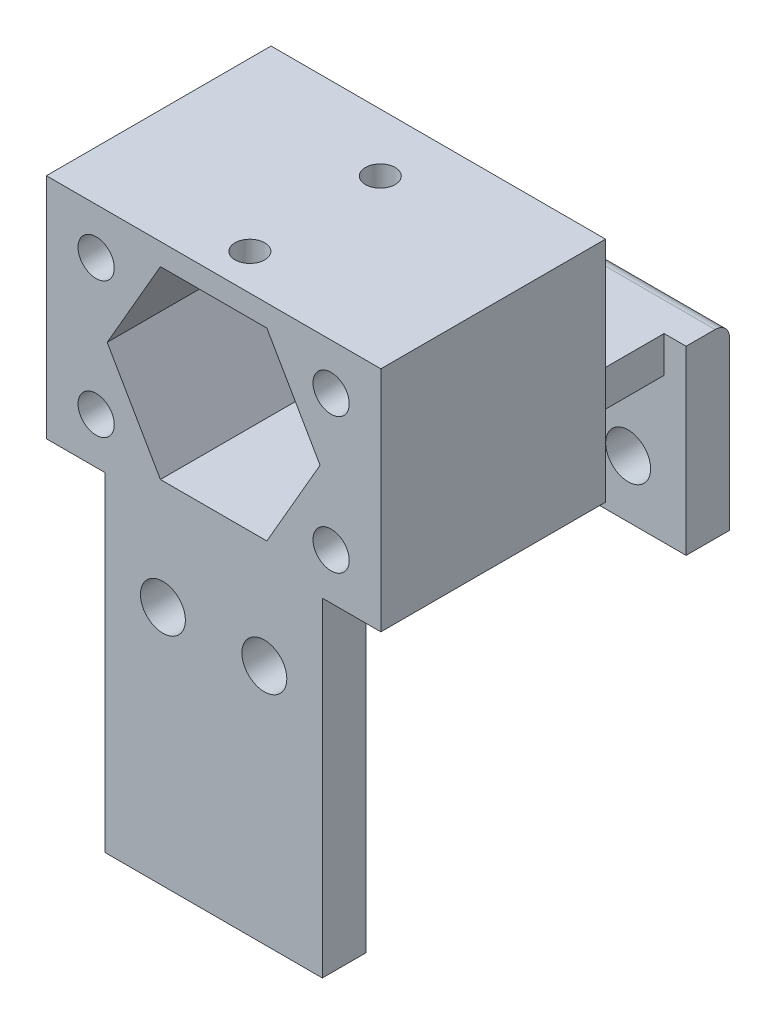
SolidWorks part; units mm, degrees
note: The reader was unsure of these and kept them because the rebuilt part matched: shared geometry of "Sketch8<2>".
other "Markup1"
sketch "Sketch23" plane through (-10.538, -17.86, 12) normal (0, 0, 1) x (1, 0, 0)
material "6061-T6 (SS)"
ref_plane "Front Plane" through (0, 0, 0) normal (0, 0, 1) x (1, 0, 0)
ref_plane "Top Plane" through (0, 0, 0) normal (0, 1, 0) x (1, 0, 0)
ref_plane "Right Plane" through (0, 0, 0) normal (1, 0, 0) x (0, 0, -1)
sketch "Sketch1" plane through (0, 0, 0) normal (0, 0, 1) x (1, 0, 0)
  line L1 (7.3439, 0) -> (3.6719, 6.36)
  line L2 (3.6719, 6.36) -> (-3.6719, 6.36)
  line L3 (-3.6719, 6.36) -> (-7.3439, 0)
  line L4 (-7.3439, 0) -> (-3.6719, -6.36)
  line L5 (-3.6719, -6.36) -> (3.6719, -6.36)
  line L6 (3.6719, -6.36) -> (7.3439, 0)
  line L7 (9.0759, 0) -> (4.538, 7.86)
  line L8 (4.538, 7.86) -> (-4.538, 7.86)
  line L9 (-4.538, 7.86) -> (-9.0759, 0)
  line L10 (-9.0759, 0) -> (-4.538, -7.86)
  line L11 (-4.538, -7.86) -> (4.538, -7.86)
  line L12 (4.538, -7.86) -> (9.0759, 0)
  circle A0 centre (0, 0) radius 6.36 construction
  circle A1 centre (0, 0) radius 7.86 construction
  dimension "D2" = 12.72
  dimension "D1" = 1.5
extrude "Boss-Extrude1" add sketch "Sketch1" along normal blind 14
sketch "Sketch2" plane through (0, 0, 0) normal (0, 0, -1) x (-1, 0, 0)
  line L0 (-4.538, 7.86) -> (4.538, 7.86) construction
  line L1 (9.0759, 0) -> (4.538, 7.86)
  line L2 (4.538, 7.86) -> (-4.538, 7.86)
  line L3 (-4.538, 7.86) -> (-9.0759, 0)
  line L4 (-9.0759, 0) -> (-4.538, -7.86)
  line L5 (-4.538, -7.86) -> (4.538, -7.86)
  line L6 (4.538, -7.86) -> (9.0759, 0)
  circle A0 centre (0, 0) radius 7.86 construction
  circle A1 centre (0, 0) radius 4.75
  dimension "D1" = 9.5
extrude "Boss-Extrude2" add sketch "Sketch2" along normal blind 1.5
sketch "Sketch8" plane through (0, 0, 14) normal (0, 0, 1) x (1, 0, 0)
  line L1 (-7.5, -17.86) -> (7.5, -17.86)
  line L3 (-9.0759, 0) -> (-4.538, -7.86)
  line L4 (-4.538, -7.86) -> (4.538, -7.86)
  line L5 (4.538, -7.86) -> (9.0759, 0)
  line L8 (-9.0759, 0) -> (-9.0759, -7.86)
  line L10 (-3.5, -13.91) -> (3.5, -13.91) construction
  line L11 (-9.0759, -7.86) -> (-7.5, -7.86)
  line L15 (0, -13.91) -> (0, -7.86) construction
  line L16 (-5.9813, -5.36) -> (-9.0759, -5.36)
  line L17 (5.9813, -5.36) -> (9.0759, -5.36)
  line L18 (-3.6719, -6.36) -> (3.6719, -6.36) construction
  line L19 (-7.5, -7.86) -> (-7.5, -17.86)
  line L20 (9.0759, 0) -> (9.0759, -7.86)
  line L21 (9.0759, -7.86) -> (7.5, -7.86)
  line L22 (7.5, -7.86) -> (7.5, -17.86)
  line L23 (-7.5, -7.86) -> (-7.5, -5.36)
  line L24 (7.5, -7.86) -> (7.5, -5.36)
  circle A2 centre (-3.5, -13.91) radius 1.55
  circle A3 centre (3.5, -13.91) radius 1.55
  line M16 (4.538, -7.86) -> (9.0759, 0)
  line M21 (-4.538, -7.86) -> (4.538, -7.86)
  dimension "D2" = 3.1
  dimension "D1" = 10
  dimension "D3" = 7
  dimension "D4" = 6.05
  dimension "D5" = 1
  dimension "D6" = 15
extrude "Boss-Extrude3" add sketch "Sketch8" against normal blind 3
extrude "Boss-Extrude4" add sketch "Sketch8<2>" against normal blind 3 from offset 25.1 separate body contours L22 L24 L17 L3 L16 L23 L19 L1 A3 A2 M16 M21 offset against normal yes
sketch "Sketch8<2>" plane through (0, 0, 14) normal (0, 0, 1) x (1, 0, 0) same geometry as "Sketch8"
sketch "Sketch9" plane through (0, 0, -1.5) normal (0, 0, -1) x (-1, 0, 0)
  line L8 (-5.9813, -5.36) -> (5.9813, -5.36)
  line L9 (5.9813, -5.36) -> (7.5, -5.36) construction
  line L10 (5.9813, -5.36) -> (4.538, -7.86) construction
  line L11 (-5.9813, -5.36) -> (-4.538, -7.86)
  line L12 (-4.538, -7.86) -> (4.538, -7.86)
  line L13 (4.538, -7.86) -> (5.9813, -5.36)
  line L15 (4.538, -7.86) -> (9.0759, 0) construction
  line L16 (-4.538, -7.86) -> (-5.9813, -5.36) construction
  line L17 (-9.0759, 0) -> (-4.538, -7.86) construction
extrude "Boss-Extrude6" add sketch "Sketch9" along normal up to surface (12.6 mm away) up to face at (5.05, -13.91, -14.1)
hole_wizard "M2.5 Tapped Hole1" positions "Sketch11" profile "Sketch12" tap size "M2.5" standard "AS"
sketch "Sketch11" plane through (0, 7.86, 0) normal (0, 1, 0) x (1, 0, 0)
  line L0 (4.538, -14) -> (-4.538, -14) construction
  line L1 (-4.538, 1.5) -> (4.538, 1.5) construction
  point P0 (0, -2.5)
  point P2 (0, -11.5)
  dimension "D1" = 2.5
  dimension "D2" = 4
sketch "Sketch12" plane through (0, 7.86, 2.5) normal (1, 0, 0) x (0, 0, 1)
  line L0 (0, 0) -> (0, 1.5)
  line L1 (0, 1.5) -> (1.025, 1.5)
  line L2 (1.025, 1.5) -> (1.025, 0)
  line L5 (1.025, 0) -> (0, 0)
  line L11 (0, -6.35) -> (0, 107.95) construction
  dimension "Thru Tap Drill Dia." = 2.05
  dimension "Thru Tap Drill Depth" = 1.5
cosmetic thread "Hole Thread1" parameters "D2"=2.5
cosmetic thread "Hole Thread2" parameters "D2"=2.5
sketch "Sketch14" plane through (0, 0, 14) normal (0, 0, 1) x (1, 0, 0)
  line L0 (-4.538, 7.86) -> (-11.538, 7.86)
  line L1 (-11.538, 7.86) -> (-11.538, -7.86)
  line L2 (-11.538, -7.86) -> (-9.0759, -7.86)
  line L4 (-9.0759, -7.86) -> (-9.0759, 0)
  line L5 (-9.0759, 0) -> (-4.538, 7.86)
  line L7 (0, -8.525) -> (0, 8.525) construction
  line L8 (9.0759, -7.86) -> (9.0759, 0)
  line L9 (11.538, -7.86) -> (9.0759, -7.86)
  line L10 (11.538, 7.86) -> (11.538, -7.86)
  line L11 (4.538, 7.86) -> (11.538, 7.86)
  line L12 (9.0759, 0) -> (4.538, 7.86)
  line L14 (-3.6719, -6.36) -> (3.6719, -6.36) construction
  dimension "D1" = 7
  dimension "D2" = 1.5
extrude "Boss-Extrude8" add sketch "Sketch14" against normal blind 5
sketch "Sketch22" plane through (0, -7.86, 0) normal (0, -1, 0) x (1, 0, 0)
  line L0 (-9.0759, 9) -> (-9.0759, -1.5) construction
  line L1 (-9.0759, 11) -> (9.0759, 11)
  line L2 (-9.0759, 11) -> (-9.0759, 9)
  line L3 (-9.0759, 9) -> (9.0759, 9)
  line L4 (9.0759, 11) -> (9.0759, 9)
  line L5 (-4.538, 11) -> (4.538, 11) construction
extrude "Boss-Extrude9" add sketch "Sketch22" against normal up to next
fillet "Fillet2" radius 1 1 edges at (0, -5.36, -14.1)
sketch "Sketch24" plane through (0, 0, 9) normal (0, 0, -1) x (-1, 0, 0)
  line L5 (-11.538, -7.86) -> (-4.538, -7.86)
  line L6 (-4.538, -7.86) -> (-9.0759, 0)
  line L7 (-9.0759, 0) -> (-4.538, 7.86)
  line L8 (-4.538, 7.86) -> (-11.538, 7.86)
  line L9 (-11.538, 7.86) -> (-11.538, -7.86)
  line L10 (-11.538, -7.86) -> (-4.538, -7.86)
  line L11 (-4.538, -7.86) -> (-9.0759, 0)
  line L12 (-9.0759, 0) -> (-4.538, 7.86)
  line L13 (-4.538, 7.86) -> (-11.538, 7.86)
  line L14 (-11.538, 7.86) -> (-11.538, -7.86)
  line L15 (4.538, 7.86) -> (9.0759, 0)
  line L16 (9.0759, 0) -> (4.538, -7.86)
  line L17 (4.538, -7.86) -> (11.538, -7.86)
  line L18 (11.538, -7.86) -> (11.538, 7.86)
  line L19 (11.538, 7.86) -> (4.538, 7.86)
  line L20 (4.538, 7.86) -> (9.0759, 0)
  line L21 (9.0759, 0) -> (4.538, -7.86)
  line L22 (4.538, -7.86) -> (11.538, -7.86)
  line L23 (11.538, -7.86) -> (11.538, 7.86)
  line L24 (11.538, 7.86) -> (4.538, 7.86)
  dimension "D1" = 0
  dimension "D2" = 0
extrude "Boss-Extrude11" add sketch "Sketch24" along normal up to surface (10.5 mm away) up to face at (0, 0.8333, -1.5)
hole_wizard "M3 Tapped Hole2" positions "Sketch21" profile "Sketch19" tap size "M3" standard "AS"
sketch "Sketch21" plane through (0, 0, 14) normal (0, 0, 1) x (1, 0, 0)
  line L0 (-5.5079, -3.18) -> (-8.106, -4.68) construction
  line L1 (-7.3439, 0) -> (-3.6719, -6.36) construction
  line L3 (-5.5079, 3.18) -> (-8.106, 4.68) construction
  line L4 (-3.6719, 6.36) -> (-7.3439, 0) construction
  line L5 (5.5079, 3.18) -> (8.106, 4.68) construction
  line L6 (7.3439, 0) -> (3.6719, 6.36) construction
  line L7 (5.5079, -3.18) -> (8.106, -4.68) construction
  line L8 (3.6719, -6.36) -> (7.3439, 0) construction
  line L9 (-3.6719, 6.36) -> (-7.3439, 0) construction
  point P0 (-8.106, 4.68)
  point P2 (-8.106, -4.68)
  point P4 (8.106, 4.68)
  point P6 (8.106, -4.68)
  dimension "D1" = 3
cosmetic thread "Hole Thread7" parameters "D1"=28.6, "D2"=3
cosmetic thread "Hole Thread8" parameters "D1"=28.6, "D2"=3
cosmetic thread "Hole Thread9" parameters "D1"=28.6, "D2"=3
cosmetic thread "Hole Thread10" parameters "D1"=28.6, "D2"=3
sketch "Sketch19" plane through (-8.106, 4.68, 14) normal (1, 0, 0) x (0, -1, 0)
  line L0 (0, 0) -> (0, 16.2511)
  line L1 (0, 16.2511) -> (1.25, 15.5)
  line L2 (1.25, 15.5) -> (1.25, 0)
  line L5 (1.25, 0) -> (0, 0)
  line L10 (0, 16.2511) -> (-1.25, 15.5) construction
  line L11 (0, -6.35) -> (0, 107.95) construction
  dimension "Tap Drill Dia." = 2.5
  dimension "Tap Drill Depth" = 15.5
  dimension "Drill Angle" = 118
sketch "Sketch25" plane through (0, 0, -1.5) normal (0, 0, -1) x (-1, 0, 0)
  line L0 (-5.9813, -5.36) -> (-5.9813, -7.86)
  line L1 (-11.538, -7.86) -> (-4.538, -7.86) construction
  line L2 (-5.9813, -7.86) -> (-4.538, -7.86)
  line L3 (-4.538, -7.86) -> (-5.9813, -5.36)
extrude "Boss-Extrude12" add sketch "Sketch25" along normal up to surface (9.6 mm away) up to face at (5.05, -13.91, -11.1)
sketch "Sketch26" plane through (0, -17.86, 0) normal (0, -1, 0) x (1, 0, 0)
  line L4 (7.5, 14) -> (-7.5, 14)
  line L5 (-7.5, 14) -> (-7.5, 11)
  line L6 (-7.5, 11) -> (7.5, 11)
  line L7 (7.5, 11) -> (7.5, 14)
  line L8 (7.5, 14) -> (-7.5, 14)
  line L9 (-7.5, 14) -> (-7.5, 11)
  line L10 (-7.5, 11) -> (7.5, 11)
  line L11 (7.5, 11) -> (7.5, 14)
  dimension "D1" = 0
extrude "Boss-Extrude13" add sketch "Sketch26" along normal blind 12.7
